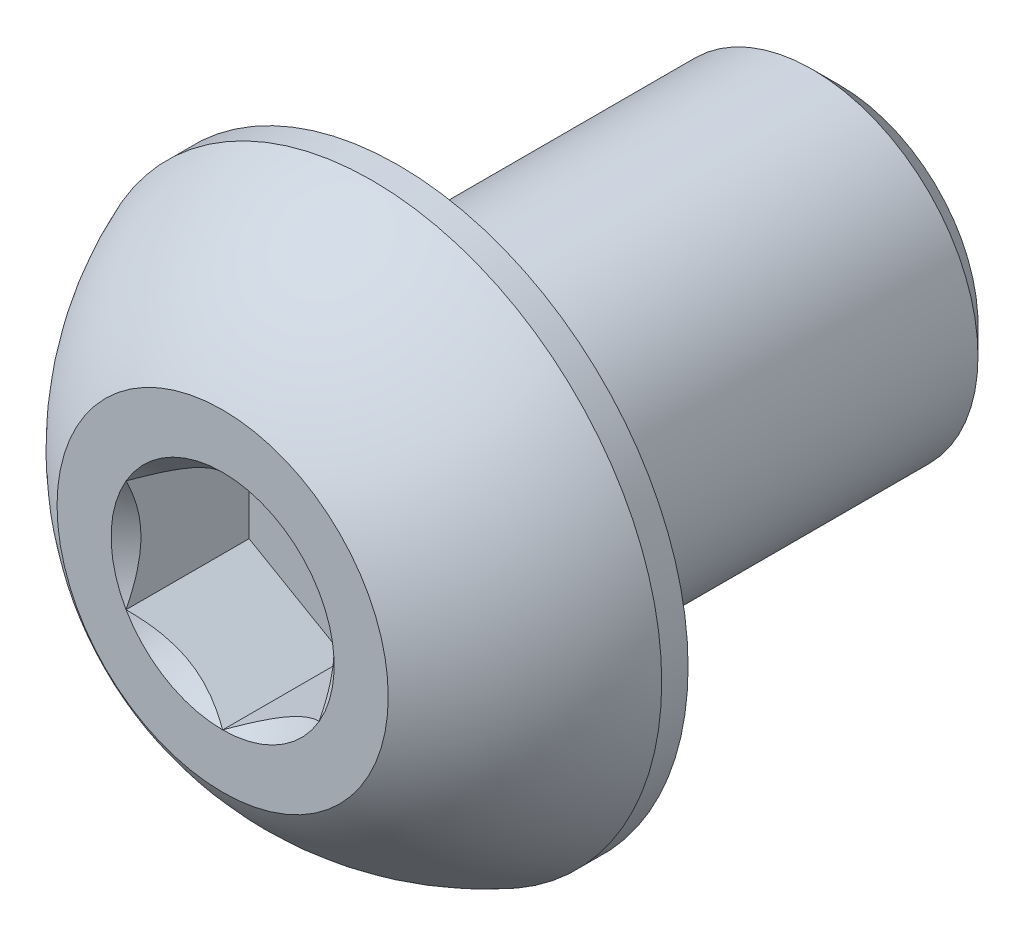
SolidWorks part; units mm, degrees
material "Plain Carbon Steel"
ref_plane "Front" through (0, 0, 0) normal (0, 0, 1) x (1, 0, 0)
ref_plane "Top" through (0, 0, 0) normal (0, 1, 0) x (1, 0, 0)
ref_plane "Right" through (0, 0, 0) normal (1, 0, 0) x (0, 0, -1)
sketch "Sketch1" plane through (0, 0, 0) normal (1, 0, 0) x (0, 0, -1)
  line L2 (5.0546, 4.7625) -> (17.7546, 4.7625)
  line L3 (17.7546, 4.7625) -> (17.7546, 0)
  line L4 (17.7546, 0) -> (5.0546, 0)
  line L6 (4.2964, 8.3312) -> (5.0546, 8.3312) construction
  line L7 (17.7546, 4.7625) -> (17.7546, -4.7625) construction
  line L8 (0, 0) -> (5.0546, 0) construction
  line L9 (5.0546, 8.3312) -> (5.0546, -8.3312) construction
  line L11 (5.0546, 4.7625) -> (5.0546, 0)
  line L13 (0, 2.7781) -> (0, -2.7781) construction
  line L14 (0, 2.7781) -> (0, 4.7625) construction
  arc A3 (0, 4.7625) -> (4.2964, 8.3312) centre (7.5862, 0) cw construction
  dimension "D1" = 0.7582
revolve "Revolve1" add sketch "Sketch1" angle 360 mid plane about L4
sketch "Sketch3" plane through (0, 0, -17.7546) normal (0, 0, -1) x (-1, 0, 0)
  circle A0 centre (0, 0) radius 4.7625
curve "Helix/Spiral1" pitch 1.0583 height 13.7583 turns 13
sketch "Sketch2" plane through (0, 0, 0) normal (1, 0, 0) x (0, 0, -1)
  line L0 (17.7546, 4.7625) -> (18.6806, 4.7625)
  line L1 (18.6806, 4.7625) -> (18.2838, 4.0751)
  line L2 (18.2838, 4.0751) -> (18.1515, 4.0751)
  line L3 (18.1515, 4.0751) -> (17.7546, 4.7625)
  line L4 (17.953, 4.4188) -> (18.4822, 4.4188) construction
  dimension "D1" = 60
  dimension "D2" = 0.1323
  dimension "D3" = 0.5292
chamfer "Chamfer1" distance 0.7937 angle 45 1 edges at (0, 4.7625, -17.7546)
sweep "Cut-Sweep1" [suppressed] cut profiles "Sketch2" path "Helix/Spiral1"
sketch "Sketch7" plane through (0, 0, 0) normal (1, 0, 0) x (0, 0, -1)
  line L6 (4.2964, 8.3312) -> (5.0546, 8.3312) construction
  line L8 (0, 0) -> (5.0546, 0) construction
  line L11 (5.0546, 8.3312) -> (5.0546, -8.3312) construction
  line L12 (4.2964, 8.3312) -> (5.0546, 8.3312)
  line L13 (0, 0) -> (5.0546, 0)
  line L14 (0, 2.7781) -> (0, -2.7781) construction
  line L15 (5.0546, 8.3312) -> (5.0546, 0)
  line L16 (0, 4.7625) -> (0, 0)
  arc A2 (4.2964, 8.3312) -> (0, 4.7625) centre (7.5862, 0) ccw construction
  arc A3 (4.2964, 8.3312) -> (0, 4.7625) centre (7.5862, 0) ccw
revolve "Revolve2" add sketch "Sketch7" angle 360 mid plane about L13
sketch "Sketch5" plane through (0, 0, 0) normal (0, 0, 1) x (1, 0, 0)
  line L1 (2.7781, -1.604) -> (2.7781, 1.604)
  line L2 (2.7781, 1.604) -> (0, 3.2079)
  line L3 (0, 3.2079) -> (-2.7781, 1.604)
  line L4 (-2.7781, 1.604) -> (-2.7781, -1.604)
  line L5 (-2.7781, -1.604) -> (0, -3.2079)
  line L6 (0, -3.2079) -> (2.7781, -1.604)
  circle A0 centre (0, 0) radius 2.7781 construction
extrude "Cut-Extrude2" cut sketch "Sketch5" against normal blind 3.5382
sketch "Sketch6" plane through (0, 0, 0) normal (0, 0, 1) x (1, 0, 0)
  circle A0 centre (0, 0) radius 3.2079
extrude "Cut-Extrude3" cut sketch "Sketch6" against normal blind 3.5382 draft 45
sketch "Sketch9" [suppressed] plane through (0, 0, -5.0546) normal (0, 0, 1) x (1, 0, 0)
  circle A2 centre (0, 0) radius 4.7625
extrude "Boss-Extrude2" [suppressed] add sketch "Sketch9" against normal offset from surface (12.7 mm away) 28.575
sketch "Sketch10" plane through (0, 0, 0) normal (1, 0, 0) x (0, 0, -1)
  line L0 (17.7546, 4.7625) -> (17.7546, -4.7625) construction
  point P0 (16.1671, -4.7625)
  dimension "D1" = 1.5875
equation "\"D3@Helix/Spiral1\" = \"Lg@Sketch1\" + \"D4@Helix/Spiral1\""
equation "\"D2@Sketch2\" = \"D4@Helix/Spiral1\" * .125"
equation "\"D3@Sketch2\" = \"D4@Helix/Spiral1\" * .5"
equation "\"D1@Chamfer1\" = \"D4@Helix/Spiral1\" * .75"
equation "\"D1@Cut-Extrude2\" = \"Head Ht@Sketch1\" * .7"
equation "\"D1@Sketch1\" = \"Head Ht@Sketch1\" * .15"
equation "\"D1@Sketch10\" = \"D4@Helix/Spiral1\" * 1.5"
equation "\"D1@Cut-Extrude3\" = \"D1@Cut-Extrude2\""
